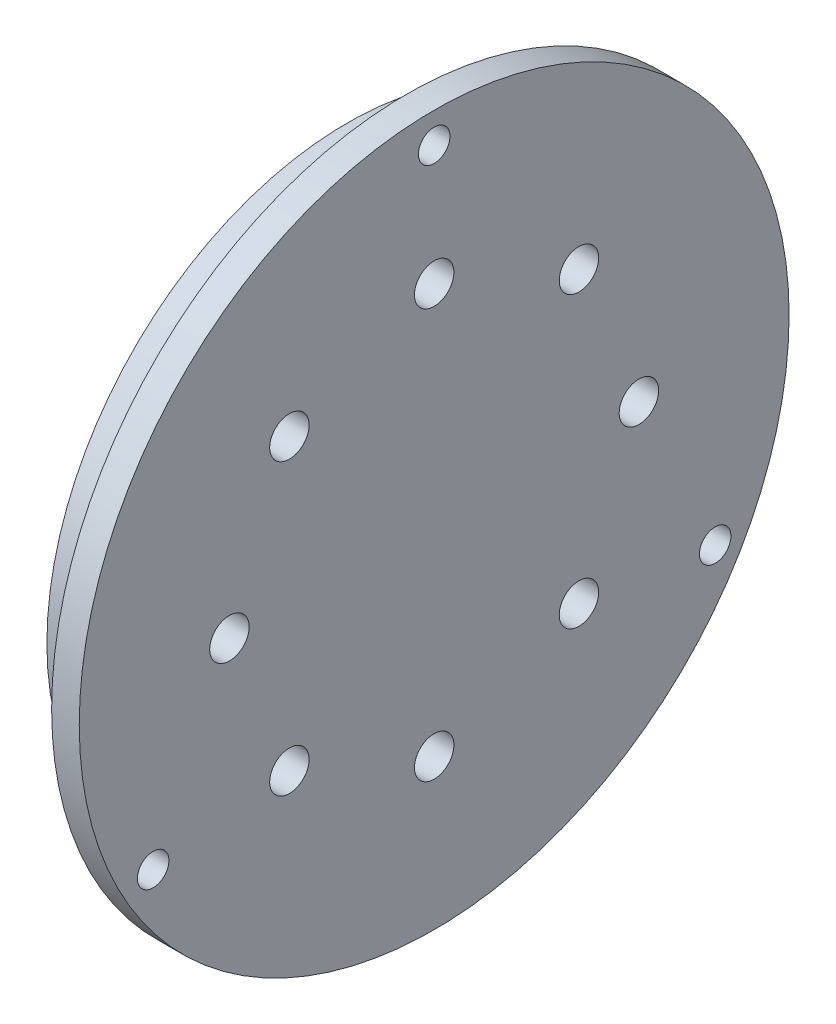
SolidWorks part; units mm, degrees
ref_plane "Front" through (0, 0, 0) normal (0, 0, 1) x (1, 0, 0)
ref_plane "Top" through (0, 0, 0) normal (0, 1, 0) x (1, 0, 0)
ref_plane "Right" through (0, 0, 0) normal (1, 0, 0) x (0, 0, -1)
sketch "Sketch1" plane through (0, 0, 0) normal (0, 0, 1) x (1, 0, 0)
  line L0 (0, 0) -> (0, 76.2)
  line L2 (15, 76.2) -> (15, 90)
  line L3 (15, 90) -> (22, 90)
  line L4 (22, 90) -> (22, 0)
  line L5 (22, 0) -> (0, 0)
  line L6 (9.8226, 76.2) -> (9.8226, 72.8466)
  line L7 (9.8226, 72.8466) -> (5.4754, 72.8466)
  line L8 (5.4754, 72.8466) -> (5.4754, 76.2)
  line L9 (15, 76.2) -> (9.8226, 76.2)
  line L10 (5.4754, 76.2) -> (0, 76.2)
  dimension "D1" = 90
  dimension "D2" = 76.2
  dimension "D3" = 7
  dimension "D4" = 15
revolve "Revolve1" add sketch "Sketch1" angle 360 about L5
sketch "Sketch2" plane through (15, 0, 0) normal (-1, 0, 0) x (0, 0, 1)
  circle A0 centre (0, 82.2773) radius 4
  point P2 (0, 83.6854)
  point P3 (0, 82.2773)
  dimension "D1" = 8
ref_axis "Axis1" through (-80.9, 0, 0) along (1, 0, 0)
extrude "Cut-Extrude1" cut sketch "Sketch2" against normal blind 10
pattern_circular "CirPattern1" count 3 over 360 about axis through (-80.9, 0, 0) along (1, 0, 0) of "Cut-Extrude1"
sketch "Sketch3" plane through (0, 0, 0) normal (-1, 0, 0) x (0, 0, 1)
  circle A0 centre (0, 51.9167) radius 5
  dimension "D1" = 10
extrude "Cut-Extrude2" cut sketch "Sketch3" against normal through all
pattern_circular "CirPattern2" count 8 over 360 about axis through (-80.9, 0, 0) along (1, 0, 0) of "Cut-Extrude2"
